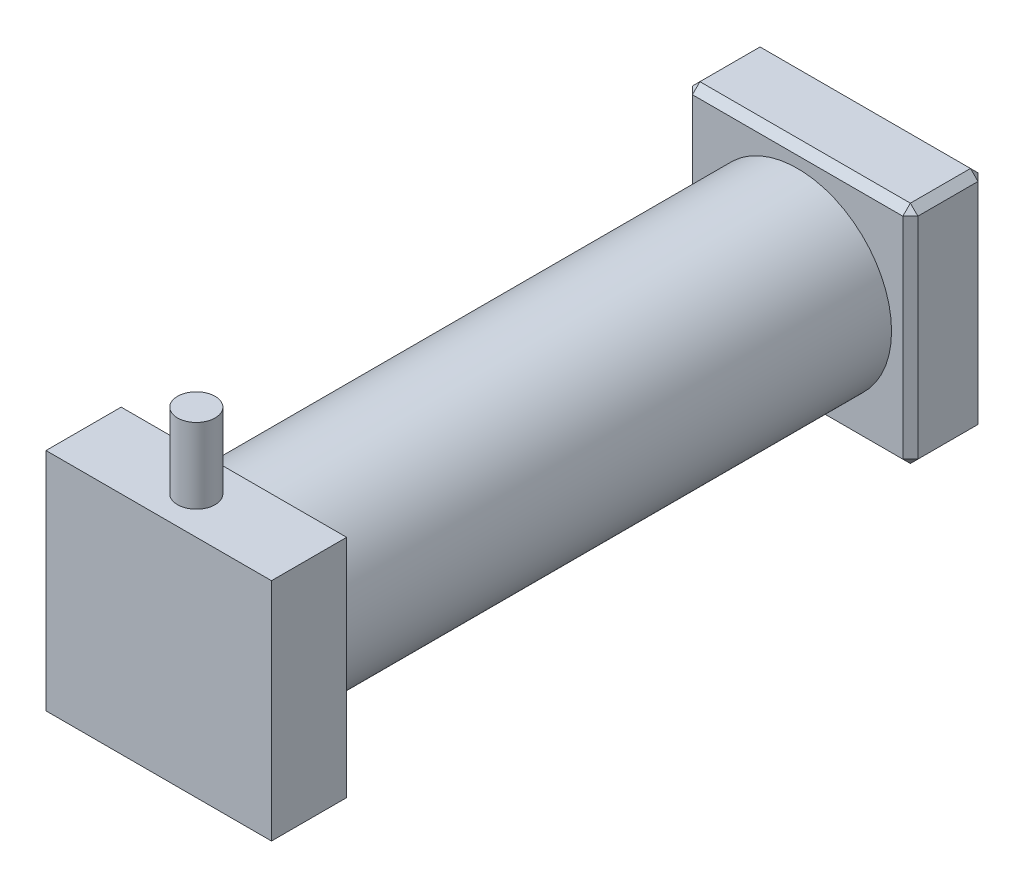
SolidWorks part; units mm, degrees
ref_plane "前视基准面" through (0, 0, 0) normal (0, 0, 1) x (1, 0, 0)
ref_plane "上视基准面" through (0, 0, 0) normal (0, 1, 0) x (1, 0, 0)
ref_plane "右视基准面" through (0, 0, 0) normal (1, 0, 0) x (0, 0, -1)
other "Configuration Table"
sketch "Sketch1" plane through (0, 0, 0) normal (0, 0, 1) x (1, 0, 0)
  circle A0 centre (0, 0) radius 25
extrude "Boss-Extrude1" add sketch "Sketch1" along normal blind 150
sketch "Sketch2" plane through (0, 0, 0) normal (0, 0, 1) x (1, 0, 0)
  line L1 (-30, -30) -> (30, -30)
  line L2 (-30, -30) -> (-30, 30)
  line L3 (-30, 30) -> (30, 30)
  line L4 (30, -30) -> (30, 30)
  line L5 (-30, -30) -> (30, 30) construction
  line L6 (-30, 30) -> (30, -30) construction
  point P0 (0, 0)
extrude "Boss-Extrude2" add sketch "Sketch2" against normal blind 20
ref_plane "Plane1" through (0, 0, 150) normal (0, 0, 1) x (1, 0, 0)
sketch "Sketch3" plane through (0, 0, 150) normal (0, 0, 1) x (1, 0, 0)
  line L1 (-30, -30) -> (30, -30)
  line L2 (-30, -30) -> (-30, 30)
  line L3 (-30, 30) -> (30, 30)
  line L4 (30, -30) -> (30, 30)
  line L5 (-30, -30) -> (30, 30) construction
  line L6 (-30, 30) -> (30, -30) construction
  point P0 (0, 0)
extrude "Boss-Extrude3" add sketch "Sketch3" along normal blind 20
ref_plane "Plane2" through (0, 0, -20) normal (0, 0, 1) x (1, 0, 0)
sketch "Sketch4" plane through (0, 0, -20) normal (0, 0, 1) x (1, 0, 0)
  circle A0 centre (0, 0) radius 25
extrude "Cut-Extrude1" cut sketch "Sketch4" along normal blind 20
ref_plane "Plane3" through (0, 30, 0) normal (0, 1, 0) x (1, 0, 0)
sketch "Sketch5" plane through (0, 30, 0) normal (0, 1, 0) x (1, 0, 0)
  circle A0 centre (0, -160) radius 5
extrude "Boss-Extrude4" add sketch "Sketch5" along normal blind 20
chamfer "Chamfer1" distance 2 angle 45 12 edges at (0, -30, -20) (-30, 0, -20) (0, 30, -20) (30, 0, -20) (0, -30, 0) (-30, -30, -10) (-30, 0, 0) (-30, 30, -10) (0, 30, 0) (30, -30, -10) (30, 0, 0) (30, 30, -10)
ref_plane "bottom_face_block" through (0, 0, -20) normal (0, 0, 1) x (1, 0, 0)
ref_plane "top_face_block" through (0, 0, 170) normal (0, 0, 1) x (1, 0, 0)
sketch3d "3DSketch1"
  line L0 (0, 0, -50) -> (0, 0, 50) construction
ref_axis "bottom_hole_axis" through (0, 0, -50) along (0, 0, 1)
sketch3d "3DSketch2"
  line L0 (0, 20, 160) -> (0, 40, 160) construction
ref_axis "top_pin_axis" through (0, 20, 160) along (0, 1, 0)
